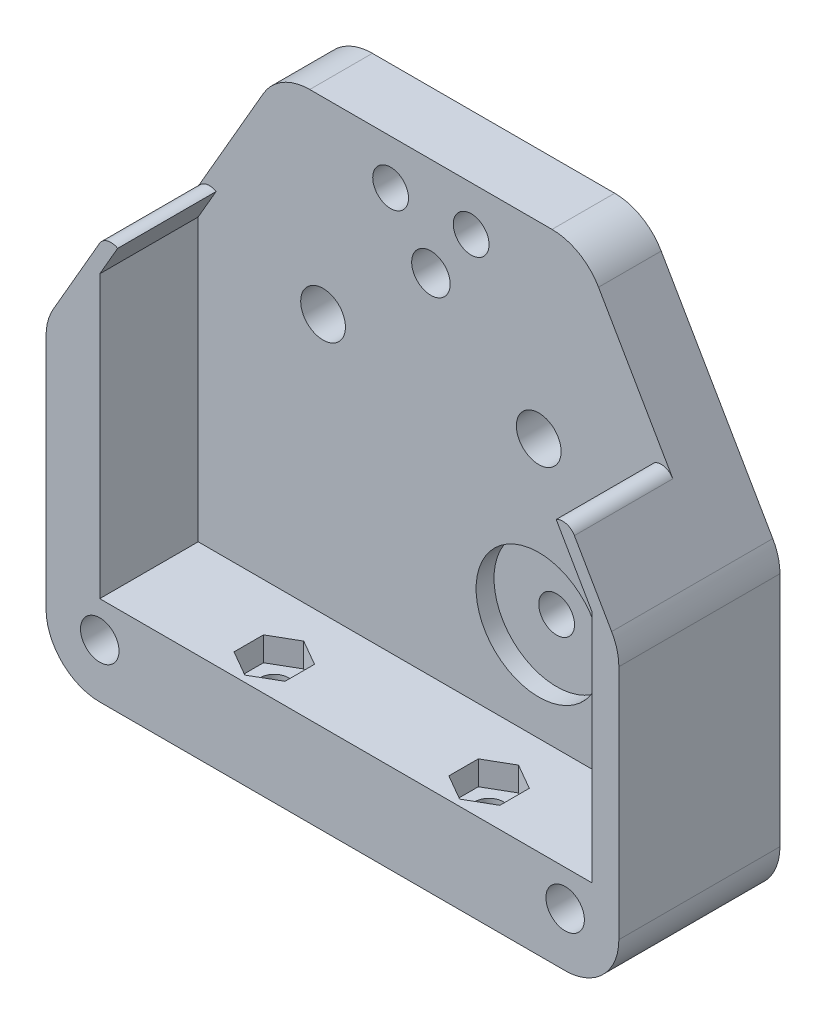
SolidWorks part; units mm, degrees
material "ABS"
ref_plane "Спереди" through (0, 0, 0) normal (0, 0, 1) x (1, 0, 0)
ref_plane "Сверху" through (0, 0, 0) normal (0, 1, 0) x (1, 0, 0)
ref_plane "Справа" through (0, 0, 0) normal (1, 0, 0) x (0, 0, -1)
sketch "Эскиз1" plane through (0, 0, 0) normal (0, 0, 1) x (1, 0, 0)
  line L0 (0, 0) -> (64, 0)
  line L1 (64, 0) -> (64, 34.0192)
  line L2 (64, 34.0192) -> (49, 60)
  line L3 (49, 60) -> (15, 60)
  line L4 (15, 60) -> (0, 34.02)
  line L5 (0, 34.02) -> (0, 0)
  dimension "D1" = 64
  dimension "D2" = 60
  dimension "D3" = 120
  dimension "D4" = 34
  dimension "D5" = 30
  dimension "D6" = 34.02
extrude "Бобышка-Вытянуть1" add sketch "Эскиз1" along normal blind 7
sketch "Эскиз3" plane through (0, 0, 7) normal (0, 0, 1) x (1, 0, 0)
  line L0 (0, 0) -> (64, 0)
  line L1 (64, 0) -> (64, 34.0192)
  line L2 (64, 34.0192) -> (58.2904, 43.9086)
  line L3 (64, 34.0192) -> (49, 60) construction
  line L4 (58.2904, 43.9086) -> (57, 43.1636)
  line L5 (57, 43.1636) -> (61, 36.2354)
  line L6 (61, 36.2354) -> (61, 10)
  line L7 (61, 10) -> (6, 10)
  line L8 (6, 10) -> (6, 41.4321)
  line L9 (6, 41.4321) -> (8, 44.8961)
  line L10 (8, 44.8961) -> (6.7097, 45.6412)
  line L11 (15, 60) -> (0, 34.02) construction
  line L12 (6.7097, 45.6412) -> (0, 34.02)
  line L13 (0, 34.02) -> (0, 0)
  dimension "D1" = 55
  dimension "D2" = 6
  dimension "D3" = 10
  dimension "D4" = 4
  dimension "D5" = 8
  dimension "D6" = 1.49
  dimension "D7" = 1.49
extrude "Бобышка-Вытянуть2" add sketch "Эскиз3" along normal blind 11
fillet "Скругление1" radius 6 6 edges at (64, 34.0192, 9) (49, 60, 3.5) (15, 60, 3.5) (0, 34.02, 9) (0, 0, 9) (64, 0, 9)
fillet "Скругление2" radius 1.49 2 edges at (58.2904, 43.9086, 12.5) (6.7097, 45.6412, 12.5)
hole_wizard "Зенковка для  винта с плоской головкой M44" positions "Эскиз13" profile "Эскиз14" countersink size "M4" standard "Ansi Metric" end condition through all
sketch "Эскиз13" plane through (0, 0, 0) normal (0, 0, -1) x (-1, 0, 0)
  line L3 (-32, 62.7004) -> (-32, -1.1162) construction
  line L5 (-45.5359, 60) -> (-18.4641, 60) construction
  line L6 (-6, 0) -> (-58, 0) construction
  line L7 (-64, 6) -> (-64, 32.4115) construction
  point P0 (-5.9999, 6)
  point P2 (-58, 6)
  point P4 (-32, 49)
  point P34 (-32, 60)
  dimension "D1" = 11
  dimension "D2" = 6
  dimension "D3" = 6
sketch "Эскиз14" plane through (5.9999, 6, 0) normal (1, 0, 0) x (0, 1, 0)
  line L0 (0, 0) -> (0, 18)
  line L1 (0, 18) -> (2.15, 18)
  line L2 (2.15, 18) -> (2.15, 2.2)
  line L3 (2.15, 2.2) -> (4.35, 0)
  line L5 (4.35, 0) -> (0, 0)
  line L6 (-2.15, 2.2) -> (-4.35, 0) construction
  line L11 (0, -3.8306) -> (0, 22.0892) construction
  dimension "Диаметр сквозного отверстия" = 4.3
  dimension "Глубина сквозного отверстия" = 18
  dimension "Диаметр передней зенковки" = 8.7
  dimension "Угол передней зенковки" = 90
hole_wizard "Отверстия под штифты Ø4.0 мм2" positions "Эскиз19" profile "Эскиз20" hole size "Ø4.0" standard "Ansi Metric" end condition through all
sketch "Эскиз19" plane through (0, 0, 0) normal (0, 0, -1) x (-1, 0, 0)
  line L0 (-45.5359, 60) -> (-18.4641, 60) construction
  line L1 (-64, 6) -> (-64, 32.4115) construction
  line L8 (-32, 62.4273) -> (-32, -3.8376) construction
  point P0 (-36.5, 55)
  point P2 (-27.4999, 55)
  point P94 (-32, 60)
  dimension "D1" = 5
  dimension "D2" = 27.5
sketch "Эскиз20" plane through (36.5, 55, 0) normal (1, 0, 0) x (0, 1, 0)
  line L0 (0, 0) -> (0, 18)
  line L1 (0, 18) -> (2, 18)
  line L2 (2, 18) -> (2, 0)
  line L5 (2, 0) -> (0, 0)
  line L11 (0, -3.866) -> (0, 11.4564) construction
  dimension "Диаметр сквозного отверстия" = 4
  dimension "Глубина сквозного отверстия" = 18
hole_wizard "Отверстия под штифты Ø5.0 мм1" positions "Эскиз21" profile "Эскиз22" hole size "Ø5.0" standard "Ansi Metric" end condition through all
sketch "Эскиз21" plane through (0, 0, 0) normal (0, 0, -1) x (-1, 0, 0)
  line L0 (-45.5359, 60) -> (-18.4641, 60) construction
  line L1 (-64, 6) -> (-64, 32.4115) construction
  line L2 (-32, 62.1722) -> (-32, -3.1086) construction
  point P0 (-44.05, 39)
  point P2 (-19.9499, 39)
  point P18 (-32, 60)
  dimension "D1" = 21
  dimension "D2" = 19.95
sketch "Эскиз22" plane through (44.05, 39, 0) normal (1, 0, 0) x (0, 1, 0)
  line L0 (0, 0) -> (0, 18)
  line L1 (0, 18) -> (2.5, 18)
  line L2 (2.5, 18) -> (2.5, 0)
  line L5 (2.5, 0) -> (0, 0)
  line L11 (0, -6.35) -> (0, 13.5001) construction
  dimension "Диаметр сквозного отверстия" = 5
  dimension "Глубина сквозного отверстия" = 18
hole_wizard "Сверло под метчик  спиральное M31" positions "Эскиз39" profile "Эскиз40" hole size "M3x0.5" standard "Ansi Metric" end condition through all
sketch "Эскиз39" plane through (0, 10, 0) normal (0, 1, 0) x (1, 0, 0)
  line L0 (0, -18) -> (0, 0) construction
  line L1 (61, -18) -> (6, -18) construction
  line L2 (33.5, -21.2954) -> (33.5, 2.3347) construction
  point P0 (21.5, -14)
  point P2 (45.5, -14)
  point P14 (33.5, -18)
  dimension "D1" = 21.5
  dimension "D2" = 4
sketch "Эскиз40" plane through (21.5, 10, 14) normal (1, 0, 0) x (0, 0, 1)
  line L0 (0, 0) -> (0, 10)
  line L1 (0, 10) -> (1.6, 10)
  line L2 (1.6, 10) -> (1.6, 0)
  line L5 (1.6, 0) -> (0, 0)
  line L11 (0, -6.35) -> (0, 15.8468) construction
  dimension "Диаметр сквозного отверстия" = 3.2
  dimension "Глубина сквозного отверстия" = 10
sketch "Эскиз41" plane through (0, 10, 0) normal (0, 1, 0) x (1, 0, 0)
  line L0 (21.5, -10.2389) -> (21.5, -18.0592) construction
  line L1 (21.5, -10.7091) -> (18.65, -12.3546)
  line L2 (18.65, -12.3546) -> (18.65, -15.6454)
  line L3 (18.65, -15.6454) -> (21.5, -17.2909)
  line L4 (21.5, -17.2909) -> (24.35, -15.6454)
  line L5 (24.35, -15.6454) -> (24.35, -12.3546)
  line L6 (24.35, -12.3546) -> (21.5, -10.7091)
  line L7 (45.5, -10.3933) -> (45.5, -17.8618) construction
  line L9 (45.5, -10.7091) -> (42.65, -12.3546)
  line L10 (42.65, -12.3546) -> (42.65, -15.6454)
  line L11 (42.65, -15.6454) -> (45.5, -17.2909)
  line L12 (45.5, -17.2909) -> (48.35, -15.6454)
  line L13 (48.35, -15.6454) -> (48.35, -12.3546)
  line L14 (48.35, -12.3546) -> (45.5, -10.7091)
  circle A0 centre (21.5, -14) radius 2.85 construction
  circle A1 centre (45.5, -14) radius 2.85 construction
  dimension "D1" = 60
  dimension "D2" = 5.7
  dimension "D3" = 60
  dimension "D4" = 5.7
extrude "Вырез-Вытянуть2" cut sketch "Эскиз41" against normal blind 2.7
ref_plane "Плоскость2" through (0, 8, 0) normal (0, -1, 0) x (-1, 0, 0)
sketch "Эскиз44" plane through (0, 8, 0) normal (0, -1, 0) x (-1, 0, 0)
  line L0 (-6, 0) -> (-58, 0) construction
  line L1 (-32, -6.7909) -> (-29.15, -5.1454)
  line L2 (-29.15, -5.1454) -> (-29.15, -1.8546)
  line L3 (-29.15, -1.8546) -> (-32, -0.2091)
  line L4 (-32, -0.2091) -> (-34.85, -1.8546)
  line L5 (-34.85, -1.8546) -> (-34.85, -5.1454)
  line L6 (-34.85, -5.1454) -> (-32, -6.7909)
  line L7 (-32, -7.4232) -> (-32, 0.5117) construction
  line L9 (0, 0) -> (0, -18) construction
  circle A0 centre (-32, -3.5) radius 2.85 construction
  dimension "D1" = 3.5
  dimension "D2" = 5.7
  dimension "D3" = 60
  dimension "D4" = 32
extrude "Вырез-Вытянуть3" cut sketch "Эскиз44" against normal blind 2.7 contours L4 L5 L6 L1 L2 L3
hole_wizard "Сверло под метчик  спиральное M33" positions "Эскиз49" profile "Эскиз50" hole size "M3x0.5" standard "Ansi Metric"
sketch "Эскиз49" plane through (0, 0, 0) normal (0, -1, 0) x (-1, 0, 0)
  line L0 (-6, 0) -> (-58, 0) construction
  line L1 (0, 0) -> (0, -18) construction
  point P0 (-32, -3.5)
  dimension "D1" = 3.5
  dimension "D2" = 32
sketch "Эскиз50" plane through (32, 0, 3.5) normal (1, 0, 0) x (0, 0, -1)
  line L0 (0, 0) -> (0, 15.9614)
  line L1 (0, 15.9614) -> (1.6, 15)
  line L2 (1.6, 15) -> (1.6, 0)
  line L5 (1.6, 0) -> (0, 0)
  line L10 (0, 15.9614) -> (-1.6, 15) construction
  line L11 (0, -4.7969) -> (0, 18.9972) construction
  dimension "Диаметр отверстия" = 3.2
  dimension "Глубина отверстия" = 15
  dimension "Угол заточки сверла" = 118
sketch "Эскиз51" plane through (0, 0, 0) normal (0, 0, -1) x (-1, 0, 0)
  line L0 (-34.85, 10.7) -> (-29.15, 10.7)
  line L1 (-29.15, 10.7) -> (-29.15, 8)
  line L2 (-29.15, 8) -> (-34.85, 8)
  line L3 (-34.85, 8) -> (-34.85, 10.7)
  line L5 (-6, 0) -> (-58, 0) construction
  line L6 (0, 32.4123) -> (0, 6) construction
  dimension "D1" = 5.7
  dimension "D2" = 2.7
  dimension "D3" = 8
  dimension "D4" = 29.15
extrude "Вырез-Вытянуть4" cut sketch "Эскиз51" against normal blind 3.5
hole_wizard "Отверстия под штифты Ø4.0 мм3" positions "Эскиз52" profile "Эскиз53" hole size "Ø4.0" standard "Ansi Metric" end condition through all
sketch "Эскиз52" plane through (0, 0, 7) normal (0, 0, 1) x (1, 0, 0)
  line L0 (64, 6) -> (64, 32.4115) construction
  line L1 (6, 0) -> (58, 0) construction
  point P0 (44.05, 21)
  dimension "D1" = 19.95
  dimension "D2" = 21
sketch "Эскиз53" plane through (44.05, 21, 7) normal (1, 0, 0) x (0, -1, 0)
  line L0 (0, 0) -> (0, 7)
  line L1 (0, 7) -> (2, 7)
  line L2 (2, 7) -> (2, 0)
  line L5 (2, 0) -> (0, 0)
  line L11 (0, -6.35) -> (0, 24.92) construction
  dimension "Диаметр сквозного отверстия" = 4
  dimension "Глубина сквозного отверстия" = 7
sketch "Эскиз54" plane through (0, 0, 7) normal (0, 0, 1) x (1, 0, 0)
  line L0 (64, 6) -> (64, 32.4115) construction
  line L1 (6, 0) -> (58, 0) construction
  circle A0 centre (44.05, 21) radius 7
  dimension "D1" = 14
  dimension "D2" = 19.95
  dimension "D3" = 21
extrude "Вырез-Вытянуть5" cut sketch "Эскиз54" against normal blind 2
